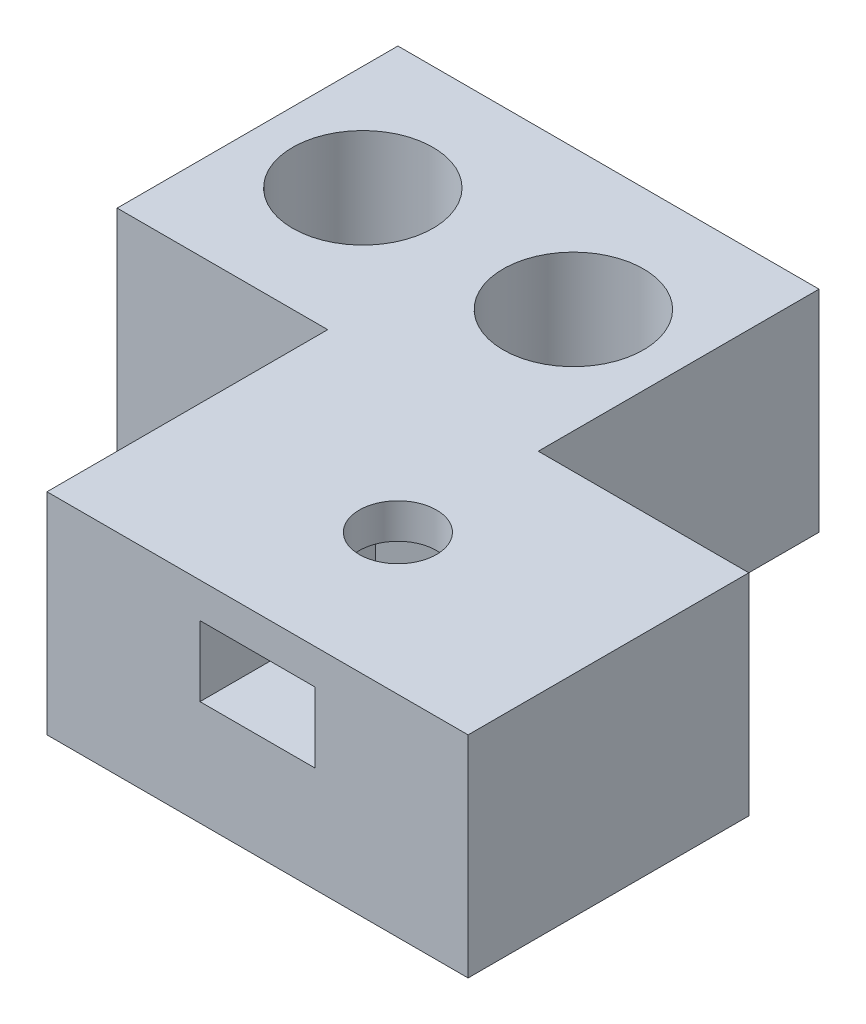
SolidWorks part; units mm, degrees
ref_plane "Front Plane" through (0, 0, 0) normal (0, 0, 1) x (1, 0, 0)
ref_plane "Top Plane" through (0, 0, 0) normal (0, 1, 0) x (1, 0, 0)
ref_plane "Right Plane" through (0, 0, 0) normal (1, 0, 0) x (0, 0, -1)
sketch "Sketch1" plane through (0, 0, 0) normal (0, 0, 1) x (1, 0, 0)
  line L1 (0, 0) -> (30, 0)
  line L2 (0, 0) -> (0, 15)
  line L3 (0, 15) -> (30, 15)
  line L4 (30, 0) -> (30, 15)
  dimension "D1" = 15
  dimension "D2" = 30
extrude "Boss-Extrude1" add sketch "Sketch1" along normal blind 20
sketch "Sketch2" plane through (0, 0, 20) normal (0, 0, 1) x (1, 0, 0)
  line L0 (30, 15) -> (0, 15) construction
  line L1 (0, 15) -> (0, 0) construction
  line L4 (10.9, 7.5) -> (19.1, 7.5)
  line L5 (10.9, 7.5) -> (10.9, 12.5)
  line L6 (10.9, 12.5) -> (19.1, 12.5)
  line L7 (19.1, 7.5) -> (19.1, 12.5)
  dimension "D7" = 5
  dimension "D8" = 8.2
  dimension "D9" = 10.9
  dimension "D10" = 2.5
extrude "Cut-Extrude1" cut sketch "Sketch2" against normal through all
sketch "Sketch3" plane through (0, 15, 0) normal (0, 1, 0) x (1, 0, 0)
  line L0 (0, -20) -> (0, 0) construction
  line L1 (30, 0) -> (0, 0) construction
  circle A0 centre (15, -10) radius 2.75
  dimension "D1" = 5.5
  dimension "D2" = 15
  dimension "D3" = 10
extrude "Cut-Extrude2" cut sketch "Sketch3" against normal through all
sketch "Sketch4" plane through (0, 7.5, 0) normal (0, 1, 0) x (1, 0, 0)
  line L0 (19.1, -7.5) -> (15.1, -5.1339)
  line L1 (19.1, 0) -> (19.1, -20) construction
  line L2 (15.1, -5.1339) -> (10.9, -7.5)
  line L3 (10.9, 0) -> (10.9, -20) construction
  line L8 (10.9, -20) -> (19.1, -20)
  line L9 (19.1, -20) -> (19.1, 0)
  line L10 (19.1, 0) -> (10.9, 0)
  line L11 (10.9, 0) -> (10.9, -20)
  line L13 (19.1, -7.5) -> (19.1, 0)
  line L14 (19.1, 0) -> (10.9, 0)
  line L15 (10.9, 0) -> (10.9, -7.5)
  point P4 (10.9, -10)
  point P9 (19.1, -10)
  dimension "D1" = 2.5
  dimension "D2" = 2.5
  dimension "D3" = 120
  dimension "D4" = 4
  dimension "D5" = 0
extrude "Boss-Extrude2" add sketch "Sketch4" along normal up to next
sketch "Sketch5" plane through (0, 0, 0) normal (0, 0, -1) x (-1, 0, 0)
  line L0 (-30, 15) -> (0, 15) construction
  line L1 (-15, 15) -> (15, 15)
  line L2 (-15, 15) -> (-15, 0)
  line L3 (-15, 0) -> (15, 0)
  line L4 (15, 15) -> (15, 0)
  point P4 (-15, 15)
  point P9 (4.1525, 15)
  dimension "D1" = 30
extrude "Boss-Extrude3" add sketch "Sketch5" along normal blind 20
sketch "Sketch6" plane through (0, 0, 0) normal (0, -1, 0) x (1, 0, 0)
  line L1 (15, -12.5) -> (-15, -12.5)
  line L2 (15, -12.5) -> (15, -7.5)
  line L3 (15, -7.5) -> (-15, -7.5)
  line L4 (-15, -12.5) -> (-15, -7.5)
  line L6 (15, -20) -> (-15, -20) construction
  line L8 (15, -20) -> (15, 0) construction
  line L9 (-15, -20) -> (-15, 0) construction
  dimension "D1" = 5
  dimension "D2" = 7.5
  dimension "D3" = 0
  dimension "D4" = 0
extrude "Boss-Extrude4" add sketch "Sketch6" along normal blind 2
sketch "Sketch7" plane through (0, 15, 0) normal (0, 1, 0) x (1, 0, 0)
  line L0 (-15, 20) -> (15, 20) construction
  line L1 (0, -20) -> (0, 0) construction
  line L2 (30, -20) -> (30, 0) construction
  circle A0 centre (7.5, 10) radius 2.75
  circle A1 centre (-7.5, 10) radius 2.75
  dimension "D1" = 5.5
  dimension "D2" = 5.5
  dimension "D4" = 10
  dimension "D6" = 37.5
  dimension "D3" = 10
  dimension "D5" = 7.5
extrude "Cut-Extrude3" cut sketch "Sketch7" against normal through all
sketch "Sketch8" plane through (0, 15, 0) normal (0, 1, 0) x (1, 0, 0)
  circle A0 centre (7.5, 10) radius 5
  circle A1 centre (-7.5, 10) radius 5
  point P6 (22.5, 10)
  dimension "D1" = 10
  dimension "D2" = 10
extrude "Cut-Extrude4" cut sketch "Sketch8" against normal offset from surface (10 mm away) 5 up to face at (15, 0, 12.75)
sketch "Sketch10" plane through (0, -2, 0) normal (0, -1, 0) x (1, 0, 0)
  circle A0 centre (-7.5, -10) radius 5
  circle A1 centre (7.5, -10) radius 5
  dimension "D1" = 10
  dimension "D2" = 10
extrude "Cut-Extrude5" cut sketch "Sketch10" against normal up to surface (2 mm away) up to face at (15, 0, 12.75)
